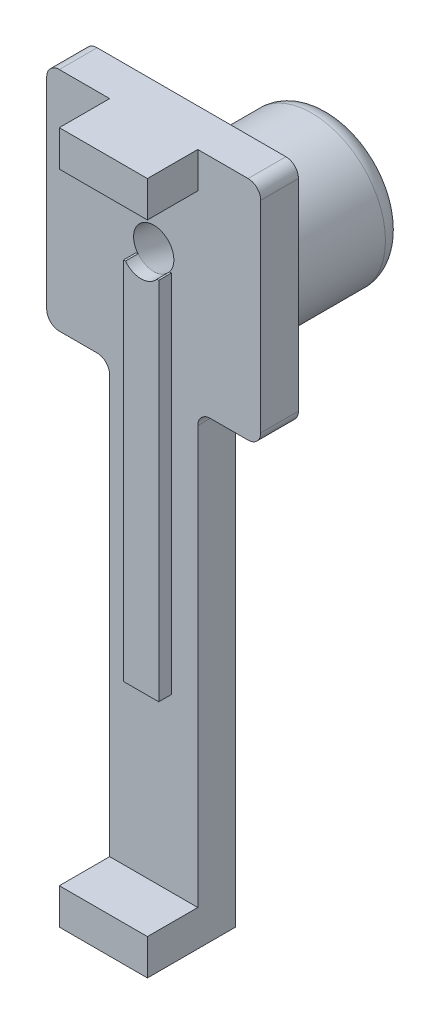
SolidWorks part; units mm, degrees
ref_plane "Front Plane" through (0, 0, 0) normal (0, 0, 1) x (1, 0, 0)
ref_plane "Top Plane" through (0, 0, 0) normal (0, 1, 0) x (1, 0, 0)
ref_plane "Right Plane" through (0, 0, 0) normal (1, 0, 0) x (0, 0, -1)
sketch "Sketch1" plane through (0, 0, 0) normal (0, 0, 1) x (1, 0, 0)
  line L1 (1.5, -15) -> (-1.5, -15)
  line L2 (1.5, -15) -> (1.5, 15)
  line L3 (1.5, 15) -> (-1.5, 15)
  line L4 (-1.5, -15) -> (-1.5, 15)
  line L5 (1.5, -15) -> (-1.5, 15) construction
  line L6 (1.5, 15) -> (-1.5, -15) construction
  line L7 (3.5, -18.4549) -> (-3.5, -18.4549)
  line L8 (3.5, -18.4549) -> (3.5, 36.5451)
  line L9 (3.5, 36.5451) -> (-3.5, 36.5451)
  line L10 (-3.5, -18.4549) -> (-3.5, 36.5451)
  line L11 (3.5, -18.4549) -> (-3.5, 36.5451) construction
  line L12 (3.5, 36.5451) -> (-3.5, -18.4549) construction
  point P0 (0, 0)
  point P6 (0, 9.0451)
  dimension "D1" = 3
  dimension "D2" = 30
  dimension "D3" = 55
  dimension "D4" = 7
extrude "Boss-Extrude1" add sketch "Sketch1" along normal blind 3 contours L10 L7 L8 L9 L1 L4 L3 L2 | L4 L1 L2 L3 region at (0, 0, 0) region at (0, -17.9005, 0)
sketch "Sketch2" plane through (0, 0, 3) normal (0, 0, 1) x (1, 0, 0)
  line L0 (3.5, -18.4549) -> (-3.5, -18.4549) construction
  line L1 (0, -2.0049) -> (0, -18.4549) construction
  line L16 (-1.4, -2.0049) -> (1.4, -2.0049)
  line L17 (-1.4, 26.9951) -> (-1.4, -2.0049)
  line L18 (1.4, 26.9951) -> (-1.4, 26.9951)
  line L19 (1.4, -2.0049) -> (1.4, 26.9951)
  point P0 (0, -2.0049)
  dimension "D1" = 16.45
  dimension "D2" = 29
  dimension "D3" = 2.8
extrude "Boss-Extrude2" add sketch "Sketch2" along normal blind 1
sketch "Sketch3" plane through (0, 0, 3) normal (0, 0, 1) x (1, 0, 0)
  line L0 (3.5, -18.4549) -> (3.5, 36.5451) construction
  line L1 (-3.5, 36.5451) -> (3.5, 36.5451)
  line L2 (-3.5, 36.5451) -> (-3.5, 33.6951)
  line L3 (-3.5, 33.6951) -> (3.5, 33.6951)
  line L4 (3.5, 36.5451) -> (3.5, 33.6951)
  line L5 (-3.5, -18.4549) -> (-3.5, 36.5451) construction
  line L6 (3.5, -18.4549) -> (-3.5, -18.4549)
  line L7 (3.5, -18.4549) -> (3.5, -15.6049)
  line L8 (3.5, -15.6049) -> (-3.5, -15.6049)
  line L9 (-3.5, -18.4549) -> (-3.5, -15.6049)
  dimension "D1" = 2.85
  dimension "D2" = 2.85
extrude "Boss-Extrude3" add sketch "Sketch3" along normal blind 4
sketch "Sketch4" plane through (-3.5, 0, 0) normal (-1, 0, 0) x (0, 0, 1)
  line L0 (3, -15.6049) -> (3, 33.6951) construction
  line L1 (0, 36.5451) -> (3, 36.5451)
  line L2 (0, 36.5451) -> (0, 18.5451)
  line L3 (0, 18.5451) -> (3, 18.5451)
  line L4 (3, 36.5451) -> (3, 18.5451)
  dimension "D1" = 18
extrude "Boss-Extrude4" add sketch "Sketch4" along normal blind 5
sketch "Sketch5" plane through (3.5, 0, 0) normal (1, 0, 0) x (0, 0, -1)
  line L4 (0, 36.5451) -> (-3, 36.5451)
  line L5 (-3, 36.5451) -> (-3, 18.5451)
  line L6 (-3, 18.5451) -> (0, 18.5451)
  line L7 (0, 18.5451) -> (0, 36.5451)
  line L8 (0, 36.5451) -> (-3, 36.5451)
  line L9 (-3, 36.5451) -> (-3, 18.5451)
  line L10 (-3, 18.5451) -> (0, 18.5451)
  line L11 (0, 18.5451) -> (0, 36.5451)
  dimension "D1" = 0
extrude "Boss-Extrude5" add sketch "Sketch5" along normal blind 5
sketch "Sketch7" plane through (0, 0, 3) normal (0, 0, 1) x (1, 0, 0)
  line L0 (-1.4, -2.0049) -> (1.4, -2.0049) construction
  circle A0 centre (0, 27.9951) radius 1.6
  dimension "D1" = 3.2
  dimension "D2" = 30
sketch "Sketch9" plane through (0, 0, 0) normal (0, 0, -1) x (-1, 0, 0)
  line L0 (0, 36.5451) -> (0, -18.4549) construction
  line L1 (-8.5, 36.5451) -> (8.5, 36.5451) construction
  line L2 (-3.5, -18.4549) -> (3.5, -18.4549) construction
  circle A0 centre (0, 25.1701) radius 5.85
  dimension "D1" = 11.7
  dimension "D2" = 11.375
extrude "Boss-Extrude7" add sketch "Sketch9" along normal blind 11.06
sketch "Sketch10" plane through (0, 0, -11.06) normal (0, 0, -1) x (-1, 0, 0)
  line L0 (0, 31.0201) -> (0, 19.3201)
  line L1 (-5.0662, 28.0951) -> (5.0662, 22.2451)
  line L2 (5.0662, 28.0951) -> (-5.0662, 22.2451)
  circle A3 centre (0, 25.1701) radius 5.85
  circle A4 centre (0, 25.1701) radius 5.85 construction
  dimension "D1" = 60
  dimension "D2" = 60
fillet "Fillet1" radius 1.5 1 edges at (-5.85, 25.1701, -11.06)
fillet "Fillet2" radius 1 6 edges at (-3.5, 18.5451, 1.5) (-8.5, 18.5451, 1.5) (-8.5, 36.5451, 1.5) (8.5, 36.5451, 1.5) (8.5, 18.5451, 1.5) (3.5, 18.5451, 1.5)
sketch "Sketch11" plane through (0, 0, -11.06) normal (0, 0, -1) x (-1, 0, 0)
  circle A0 centre (0, 25.1701) radius 3.4369
ref_plane "Plane1" through (0, 0, 0) normal (1, 0, 0) x (0, 0, -1)
loft "Cut-Loft6" cut profiles "Sketch11", "Sketch7" connector at (-1.5699, 28.2275, -11.06) connector at (0.7567, 29.4049, 3)
sketch "Sketch18" plane through (0, 0, 3) normal (0, 0, -1) x (-1, 0, 0)
  line L1 (1.2491, 26.9951) -> (-1.2488, 26.9951)
  line L2 (1.2491, 26.9951) -> (-1.2488, 26.9951)
  arc A0 (-1.2488, 26.9951) -> (1.2491, 26.9951) centre (0.0002, 27.9951) ccw
  arc A1 (-1.2488, 26.9951) -> (1.2491, 26.9951) centre (0.0002, 27.9951) ccw
  dimension "D1" = 0
extrude "Cut-Extrude1" cut sketch "Sketch18" against normal blind 10
